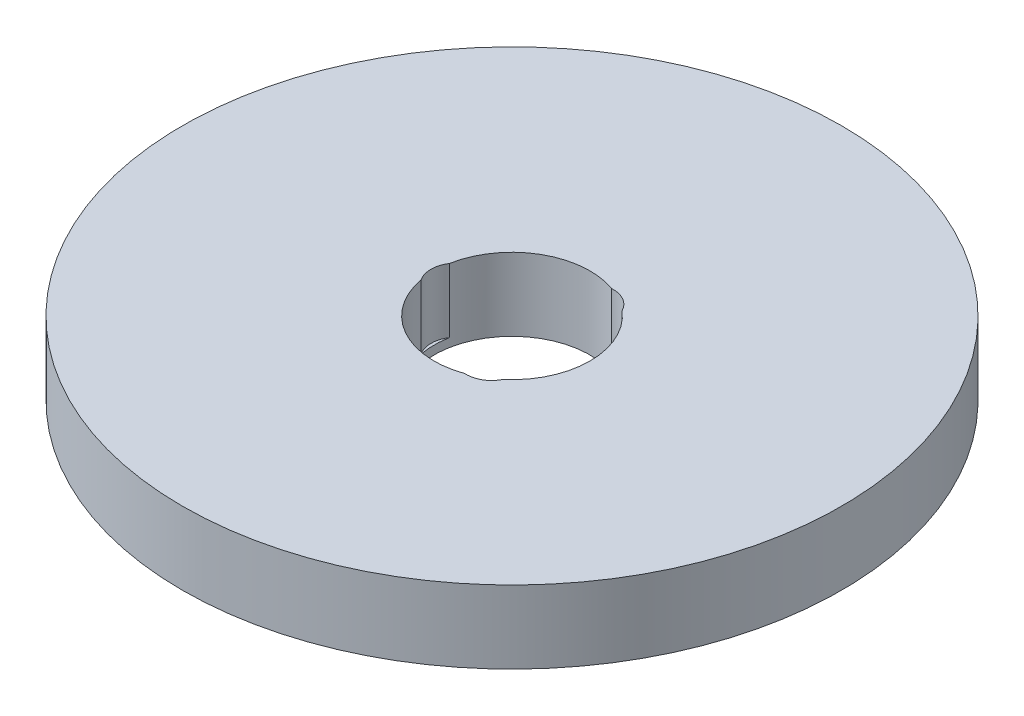
SolidWorks part; units mm, degrees
ref_plane "Front Plane" through (0, 0, 0) normal (0, 0, 1) x (1, 0, 0)
ref_plane "Top Plane" through (0, 0, 0) normal (0, 1, 0) x (1, 0, 0)
ref_plane "Right Plane" through (0, 0, 0) normal (1, 0, 0) x (0, 0, -1)
sketch "Sketch1" plane through (0, 0, 0) normal (0, 1, 0) x (1, 0, 0)
  circle A0 centre (0, 0) radius 95
  dimension "FLANGE_OD" = 190
extrude "Boss-Extrude1" add sketch "Sketch1" along normal blind 21
sketch "Sketch2" plane through (0, 0, 0) normal (0, 1, 0) x (1, 0, 0)
  circle A0 centre (0, 0) radius 22.5
  dimension "BORE_D" = 45
extrude "Cut-Extrude1" cut sketch "Sketch2" along normal through all
sketch "Sketch3" plane through (0, 21, 0) normal (0, 1, 0) x (1, 0, 0)
  circle A0 centre (0, 0) radius 15.9587 construction
  circle A1 centre (-15.9587, 0) radius 7.3839
  dimension "BOLT_D" = 14.7679
  dimension "BOLT_PCD" = 31.9175
extrude "Cut-Extrude2" cut sketch "Sketch3" against normal blind 18.5219
pattern_circular "CirPattern1" count 3 over 360 about axis through (0, 0, 0) along (0, 1, 0) of "Cut-Extrude2"
